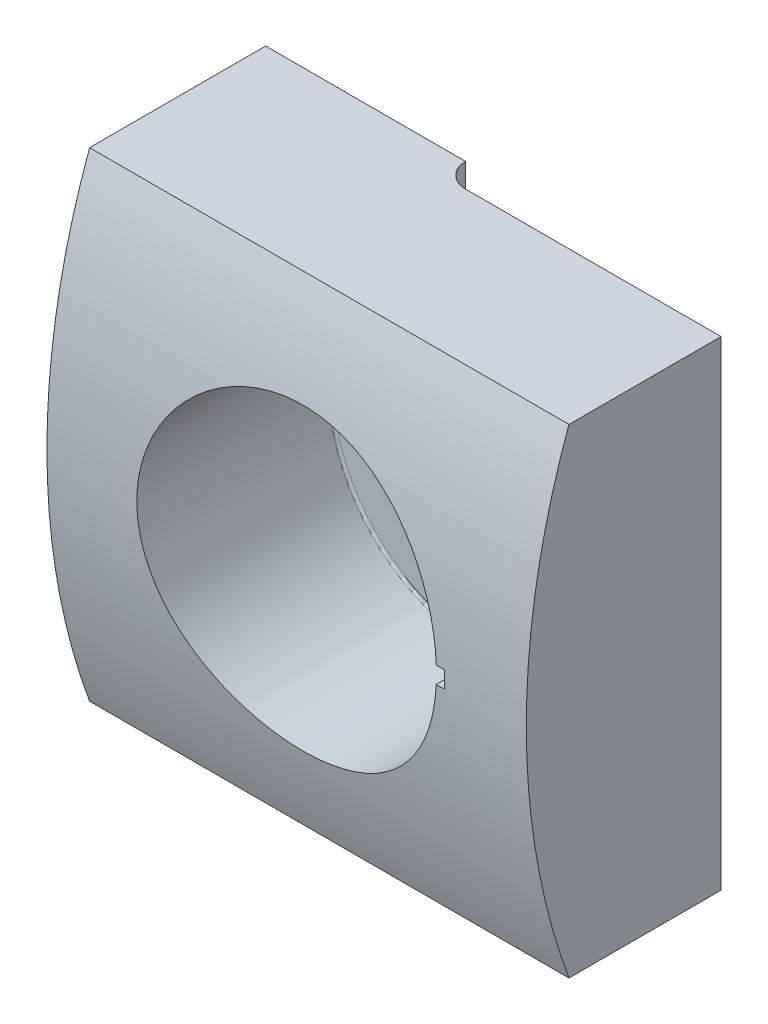
SolidWorks part; units mm, degrees
ref_plane "Front Plane" through (0, 0, 0) normal (0, 0, 1) x (1, 0, 0)
ref_plane "Top Plane" through (0, 0, 0) normal (0, 1, 0) x (1, 0, 0)
ref_plane "Right Plane" through (0, 0, 0) normal (1, 0, 0) x (0, 0, -1)
sketch "Sketch1" plane through (0, 0, 0) normal (0, 0, 1) x (1, 0, 0)
  line L6 (0, 0) -> (50.8, 0)
  line L7 (0, 0) -> (0, 50.8)
  line L8 (0, 50.8) -> (50.8, 50.8)
  line L9 (50.8, 0) -> (50.8, 50.8)
  circle A1 centre (25.4, 25.4) radius 15.875
  point P9 (25.4, 50.8)
  point P12 (50.8, 25.4)
  dimension "D1" = 31.75
  dimension "D2" = 50.8
  dimension "D3" = 50.8
extrude "Boss-Extrude1" add sketch "Sketch1" along normal blind 20.6375
sketch "Sketch3" plane through (0, 0, 0) normal (-1, 0, 0) x (0, 0, 1)
  line L6 (16.1196, 50.8) -> (20.6375, 50.8)
  line L7 (16.1196, 50.8) -> (20.6375, 50.8)
  line L8 (20.6375, 0) -> (16.1196, 0)
  line L11 (20.6375, 0) -> (20.6375, 50.8)
  arc A1 (16.1196, 0) -> (16.1196, 50.8) centre (-53.0225, 25.4) ccw
  line M4 (0, 0) -> (20.6375, 0)
  line M5 (20.6375, 0) -> (20.6375, 50.8)
  line M6 (20.6375, 50.8) -> (0, 50.8)
  dimension "D1" = 73.66
extrude "Cut-Extrude1" cut sketch "Sketch3" against normal through all contours M6 | M5 M4 region at (0, 6.3104, 19.2896) region at (0, 44.4896, 19.2896)
sketch "Sketch4" plane through (0, 0, 0) normal (0, 0, -1) x (-1, 0, 0)
  line L1 (-38.2926, 26.1976) -> (-42.1074, 26.1976)
  line L2 (-38.2926, 26.1976) -> (-38.2926, 24.4196)
  line L3 (-38.2926, 24.4196) -> (-42.1074, 24.4196)
  line L4 (-42.1074, 26.1976) -> (-42.1074, 24.4196)
  dimension "D1" = 1.778
extrude "Cut-Extrude2" cut sketch "Sketch4" against normal through all
sketch "Sketch5" plane through (0, 0, 0) normal (0, 0, -1) x (-1, 0, 0)
  line L1 (-21.1931, 50.8) -> (0, 50.8)
  line L2 (-21.1931, 50.8) -> (-21.1931, 0)
  line L3 (-21.1931, 0) -> (0, 0)
  line L4 (0, 50.8) -> (0, 0)
  line L5 (0, 50.8) -> (0, 0) construction
  line L6 (0, 0) -> (-50.8, 0) construction
  line L7 (-50.8, 50.8) -> (0, 50.8) construction
  circle A2 centre (-25.4, 25.4) radius 11.7075 construction
extrude "Boss-Extrude2" add sketch "Sketch5" along normal blind 2.54
fillet "Fillet1" radius 2.54 2 edges at (21.1931, 45.7537, 0) (21.1931, 5.0463, 0)
fillet "Fillet2" radius 2.54 2 edges at (21.1931, 10.0926, -1.27) (21.1931, 40.7074, -1.27)
fillet "Fillet3" radius 0.254 1 edges at (9.525, 25.4, 0)
